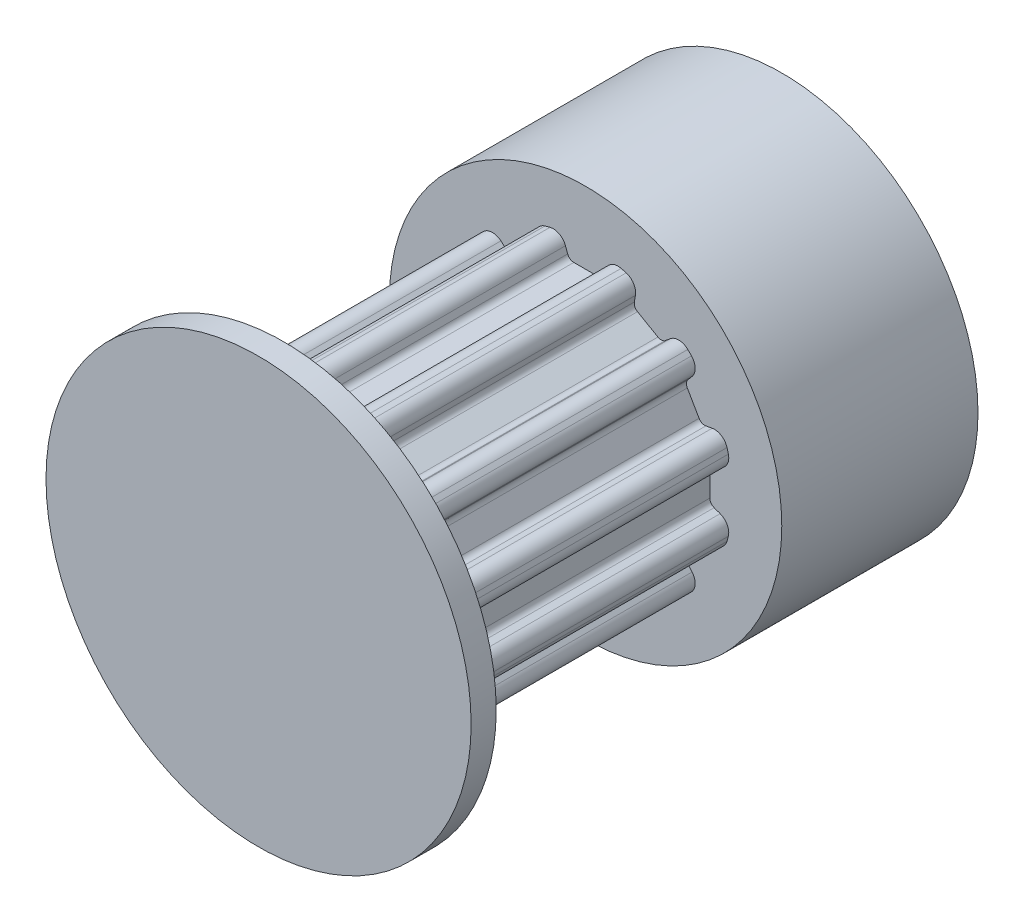
SolidWorks part; units mm, degrees
ref_plane "Front" through (0, 0, 0) normal (0, 0, 1) x (1, 0, 0)
ref_plane "Top" through (0, 0, 0) normal (0, 1, 0) x (1, 0, 0)
ref_plane "Right" through (0, 0, 0) normal (1, 0, 0) x (0, 0, -1)
sketch "support-front-body" plane through (0, 0, 0) normal (0, 0, 1) x (1, 0, 0)
  line L0 (0, 0) -> (0, 4.5) construction
  line L1 (0, 0) -> (0, -4.5) construction
  line L2 (0, 0) -> (4.5, 0) construction
  line L3 (0, 0) -> (-4.5, 0) construction
  circle A0 centre (0, 0) radius 4.5
  dimension "diam-outer" = 9
sketch "support-right-body" plane through (0, 0, 0) normal (1, 0, 0) x (0, 0, -1)
  line L0 (0, 0) -> (10, 0) construction
  line L1 (0, 4.5) -> (10, 4.5)
  line L2 (0, 4.5) -> (0, -4.5)
  line L3 (0, -4.5) -> (10, -4.5)
  line L4 (10, 4.5) -> (10, -4.5)
  dimension "length" = 10
sketch "support-right-chamfer" plane through (0, 0, 0) normal (1, 0, 0) x (0, 0, -1)
  line L0 (0, 0) -> (10, 0) construction
  line L1 (0, -4.5) -> (0, -3.5)
  line L2 (0, 4.5) -> (0, -4.5) construction
  line L4 (0, -3.5) -> (1, -4.5)
  line L5 (0, -4.5) -> (10, -4.5) construction
  line L7 (1, -4.5) -> (0, -4.5)
  line L9 (10, -4.5) -> (9, -4.5)
  line L11 (9, -4.5) -> (10, -3.5)
  line L12 (10, 4.5) -> (10, -4.5) construction
  line L14 (10, -3.5) -> (10, -4.5)
  dimension "height-chamfer-front" = 1
  dimension "angle-chamfer-front" = 45
  dimension "angle-chamfer-back" = 45
  dimension "height-chamfer-back" = 1
sketch "support-right-hub" plane through (0, 0, 0) normal (1, 0, 0) x (0, 0, -1)
  line L0 (16, 0) -> (10, 0) construction
  line L1 (10, 6) -> (16, 6)
  line L2 (10, 6) -> (10, -6)
  line L3 (10, -6) -> (16, -6)
  line L4 (16, 6) -> (16, -6)
  line L6 (0, 0) -> (10, 0) construction
  line L8 (0, 4.5) -> (0, -4.5) construction
  dimension "diam-hub" = 12
  dimension "length-hub" = 6
  dimension "dist-hub" = 10
sketch "support-right-bore" plane through (0, 0, 0) normal (1, 0, 0) x (0, 0, -1)
  line L0 (0, 4.5) -> (0, -4.5) construction
  line L1 (0, 2) -> (16, 2)
  line L2 (0, 2) -> (0, -2)
  line L3 (0, -2) -> (16, -2)
  line L4 (16, 2) -> (16, 0)
  line L5 (16, 0) -> (0, 0) construction
  line L6 (0, 0) -> (10, 0) construction
  line L7 (16, 0) -> (16, -2)
  line L8 (16, -2) -> (16, 2) construction
  dimension "diam-bore" = 4
  dimension "length-bore" = 16
  dimension "angle-bore-bottom" = 180
  dimension "angle-bore" = 90
sketch "support-stop-screw-hole" plane through (0, 0, 0) normal (1, 0, 0) x (0, 0, -1)
  line L1 (6.5667, 11) -> (9.4333, 11)
  line L2 (6.5667, 11) -> (6.5667, -1)
  line L3 (8, -1) -> (9.4333, -1)
  line L4 (9.4333, 11) -> (9.4333, -1)
  line L5 (8, -1) -> (8, 11) construction
  line L6 (8, -1) -> (6.5667, -1)
  line L7 (0, 0) -> (8, 0) construction
  line L8 (0, 4.5) -> (0, -4.5) construction
  dimension "diam-stop-screw-hole" = 2.8665
  dimension "dist-stop-screw-hole" = 8
  dimension "depth-stop-screw-hole" = 12
  dimension "angle-stop-screw-hole" = 180
  dimension "height-stop-screw-hole" = 11
sketch "support-front-keygroove" plane through (0, 0, 0) normal (0, 0, 1) x (1, 0, 0)
  line L0 (0, 0) -> (0, -2) construction
  line L1 (-1, 6) -> (1, 6)
  line L2 (-1, 6) -> (-1, 3.8)
  line L3 (-1, 3.8) -> (1, 3.8)
  line L4 (1, 6) -> (1, 3.8)
  line L5 (0, 0) -> (0, 2) construction
  circle A0 centre (0, 0) radius 2 construction
  dimension "width-keygroove" = 2
  dimension "dist-keygroove" = 8
  dimension "height-keygroove" = 2.2
sketch "support-front-tooth" plane through (0, 0, 0) normal (0, 0, 1) x (1, 0, 0)
  line L0 (0.5479, 3.9316) -> (0.6148, 4.1153)
  line L1 (0, 0) -> (0, 4.5) construction
  line L2 (-0.5479, 3.9316) -> (-0.6148, 4.1153)
  line L3 (-0.36, 3.8) -> (0.36, 3.8)
  line L4 (0, 3.8) -> (-1.0873, 4.3667) construction
  line L5 (0, 3.8) -> (-0.5479, 3.9316) construction
  line L6 (0, 4.5) -> (0.549, 4.3412) construction
  line L7 (0, 4.5) -> (2.4016, 3.8056) construction
  line L8 (0, 4.3667) -> (0, 3.8) construction
  line L9 (1.0873, 4.3667) -> (-1.0873, 4.3667) construction
  line L10 (0, 4.3667) -> (0, 4.9333) construction
  line L11 (0, 0) -> (1.2008, 4.1528) construction
  line L12 (1.411, 4.2731) -> (1.7134, 4.7523)
  line L13 (1.7134, 4.7523) -> (3.5524, 3.5917)
  line L14 (3.5524, 3.5917) -> (3.25, 3.1125)
  line L15 (2.3324, 3.0215) -> (2.7162, 3.1521)
  line L16 (2.3324, 3.0215) -> (1.7236, 3.4057)
  line L17 (1.0873, 4.3667) -> (1.0873, 4.9333)
  line L21 (-1.0873, 4.9333) -> (-1.0873, 4.3667)
  line L22 (1.0873, 4.9333) -> (-1.0873, 4.9333)
  line L23 (1.7236, 3.4057) -> (1.6764, 3.8083)
  line L24 (1.411, 4.2731) -> (1.0873, 4.3667) construction
  line L25 (-0.5479, 3.9316) -> (-0.5, 3.8) construction
  line L26 (-0.5, 3.8) -> (0.5, 3.8) construction
  line L27 (0.5, 3.8) -> (0.5479, 3.9316) construction
  line L28 (0.549, 4.3412) -> (0.9906, 3.9785) construction
  arc A0 (-0.5479, 3.9316) -> (-0.36, 3.8) centre (-0.36, 4) ccw
  circle A1 centre (0, 0) radius 4.5 construction
  arc A2 (0.6148, 4.1153) -> (1.0873, 4.3667) centre (0.9906, 3.9785) cw
  arc A3 (-0.6148, 4.1153) -> (-1.0873, 4.3667) centre (-0.9906, 3.9785) ccw
  arc A4 (0.5479, 3.9316) -> (0.36, 3.8) centre (0.36, 4) cw
  circle A5 centre (0, 0) radius 4.5 construction
  arc A6 (1.6764, 3.8083) -> (1.411, 4.2731) centre (1.2855, 3.8933) ccw
  arc A7 (2.7162, 3.1521) -> (3.25, 3.1125) centre (2.9611, 2.8359) cw
  dimension "D3" = 0.4
  dimension "D2" = 40
  dimension "D1" = 0.2
  dimension "D4" = 1
  dimension "height-tooth" = 0.7
  dimension "pitch" = 2.5
sketch "support-right-flange" plane through (0, 0, 0) normal (1, 0, 0) x (0, 0, -1)
  line L0 (0, 3.25) -> (0, 5.4167)
  line L1 (10, 4.5) -> (10, -4.5) construction
  line L2 (0, 5.4167) -> (1, 5.4167) construction
  line L3 (1, 5.4167) -> (1, 6.5)
  line L4 (0, 6.5) -> (1, 6.5)
  line L5 (1, 5.4167) -> (1, 3.25)
  line L6 (1, 3.25) -> (0, 3.25)
  line L7 (5, 4.5) -> (5, 0) construction
  line L8 (0, 4.5) -> (10, 4.5) construction
  line L9 (0, 5.4167) -> (0, 6.5)
  line L10 (9, 3.25) -> (10, 3.25)
  line L11 (9, 5.4167) -> (9, 3.25)
  line L12 (10, 6.5) -> (9, 6.5)
  line L13 (9, 5.4167) -> (9, 6.5)
  line L14 (10, 5.4167) -> (10, 6.5)
  line L15 (10, 3.25) -> (10, 5.4167)
  line L16 (10, 0) -> (0, 0) construction
  line L17 (10, -3.25) -> (10, -5.4167)
  line L18 (10, -5.4167) -> (10, -6.5)
  line L19 (9, -5.4167) -> (9, -6.5)
  line L20 (10, -6.5) -> (9, -6.5)
  line L21 (9, -5.4167) -> (9, -3.25)
  line L22 (9, -3.25) -> (10, -3.25)
  line L23 (1, -3.25) -> (0, -3.25)
  line L24 (1, -5.4167) -> (1, -3.25)
  line L25 (0, -6.5) -> (1, -6.5)
  line L26 (1, -5.4167) -> (1, -6.5)
  line L27 (0, -5.4167) -> (0, -6.5)
  line L28 (0, -3.25) -> (0, -5.4167)
  line L29 (0, 0) -> (10, 0) construction
  line L30 (0, 5.4167) -> (1, 5.4167) construction
  line L31 (0.5, 3.25) -> (0.5, 4.3333) construction
  line L32 (0.5, 4.3333) -> (0.5, 5.4167) construction
  line L33 (0.5, 6.5) -> (0.5, 5.4167) construction
  line L34 (0, 4.5) -> (10, 4.5) construction
  dimension "angle-flange" = 180
  dimension "thickness-flange" = 1
  dimension "diam-flange-inner" = 6.5
  dimension "diam-flange-outer" = 13
  dimension "width-flange-inner" = 8
sketch "support-right-flange-profile" plane through (0, 0, 0) normal (1, 0, 0) x (0, 0, -1)
  line L0 (0.7668, 6.5) -> (1, 6.5)
  line L2 (1, 6.5) -> (1, 6)
  line L3 (1, 5.4167) -> (1, 3.25) construction
  line L4 (1, 6) -> (0.7668, 6.5)
  line L5 (0, 0) -> (10, 0) construction
  line L6 (5, 0) -> (5, 4.5) construction
  line L7 (9, 6) -> (9.2332, 6.5)
  line L8 (9, 6.5) -> (9, 6)
  line L9 (9.2332, 6.5) -> (9, 6.5)
  dimension "D1" = 25
  dimension "D2" = 0.5
ref_axis "ref-axis-center" through (0, 0, -10) along (0, 0, 1)
ref_plane "ref-plane-front" through (0, 0, 0) normal (0, 0, 1) x (1, 0, 0)
ref_plane "ref-plane-back" through (0, 0, -10) normal (0, 0, 1) x (1, 0, 0)
ref_plane "ref-plane-hub-front" through (0, 0, -10) normal (0, 0, 1) x (1, 0, 0)
ref_plane "ref-plane-hub-back" through (0, 0, -16) normal (0, 0, 1) x (1, 0, 0)
ref_plane "ref-plane-bore-front" through (0, 0, 0) normal (0, 0, 1) x (1, 0, 0)
ref_plane "ref-plane-bore-back" through (0, 0, -16) normal (0, 0, 1) x (1, 0, 0)
ref_plane "ref-plane-stop-screw-hole-top" through (0, 11, 0) normal (0, 1, 0) x (-1, 0, 0)
ref_axis "ref-axis-stop-screw-hole" through (0, 11, -8) along (0, -1, 0)
sketch "Sketch5" plane through (0, 0, 0) normal (1, 0, 0) x (0, 0, -1)
  line L0 (10, 4.5) -> (10, -4.5) construction
  line L1 (0, 4.5) -> (10, 4.5) construction
  line L2 (0, 4.5) -> (0, -4.5) construction
  line L3 (0, 0) -> (10, 0) construction
  line L4 (10, 4.5) -> (10, 0)
  line L5 (0, 4.5) -> (10, 4.5)
  line L6 (0, 4.5) -> (0, 0)
  line L7 (0, 0) -> (10, 0) construction
  line L8 (0, 0) -> (10, 0)
revolve "body" add sketch "Sketch5" angle 360 about L7
sketch "Sketch11" plane through (0, 0, 0) normal (1, 0, 0) x (0, 0, -1)
  line L0 (0, -4.5) -> (0, -3.5) construction
  line L3 (1, -4.5) -> (0, -4.5) construction
  line L5 (0, -3.5) -> (1, -4.5) construction
  line L8 (0, -4.5) -> (0, -3.5)
  line L9 (1, -4.5) -> (0, -4.5)
  line L10 (0, -3.5) -> (1, -4.5)
  line L11 (0, 0) -> (10, 0) construction
  line L12 (0, 0) -> (10, 0) construction
revolve "cut-chamfer-front" [suppressed] cut sketch "Sketch11" angle 360 about L12
sketch "Sketch13" plane through (0, 0, 0) normal (1, 0, 0) x (0, 0, -1)
  line L0 (0, 0) -> (10, 0) construction
  line L1 (10, -4.5) -> (9, -4.5) construction
  line L2 (10, -3.5) -> (10, -4.5) construction
  line L3 (9, -4.5) -> (10, -3.5) construction
  line L4 (0, 0) -> (10, 0) construction
  line L5 (10, -4.5) -> (9, -4.5)
  line L6 (10, -3.5) -> (10, -4.5)
  line L7 (9, -4.5) -> (10, -3.5)
revolve "cut-chamfer-back" [suppressed] cut sketch "Sketch13" angle 360 about L4
sketch "Sketch16" plane through (0, 0, 0) normal (1, 0, 0) x (0, 0, -1)
  line L0 (16, 6) -> (16, -6) construction
  line L1 (10, 6) -> (16, 6) construction
  line L2 (16, 0) -> (10, 0) construction
  line L3 (10, 6) -> (10, -6) construction
  line L4 (16, 6) -> (16, 0)
  line L5 (10, 6) -> (16, 6)
  line L6 (16, 0) -> (10, 0) construction
  line L7 (10, 6) -> (10, 0)
  line L8 (16, 0) -> (10, 0)
revolve "body-hub" add sketch "Sketch16" angle 360 about L6
sketch "Sketch17" plane through (0, 0, 0) normal (1, 0, 0) x (0, 0, -1)
  line L0 (16, 2) -> (16, 0) construction
  line L1 (16, 0) -> (0, 0) construction
  line L2 (0, 2) -> (16, 2) construction
  line L3 (0, 2) -> (0, -2) construction
  line L4 (16, 2) -> (16, 0)
  line L5 (16, 0) -> (0, 0) construction
  line L6 (0, 2) -> (16, 2)
  line L7 (0, 2) -> (0, 0)
  line L8 (16, 0) -> (0, 0)
revolve "body-bore" [suppressed] cut sketch "Sketch17" angle 360 about L5
sketch "Sketch19" plane through (0, 0, 0) normal (1, 0, 0) x (0, 0, -1)
  line L0 (6.5667, 11) -> (9.4333, 11) construction
  line L1 (8, -1) -> (8, 11) construction
  line L2 (9.4333, 11) -> (9.4333, -1) construction
  line L3 (8, -1) -> (9.4333, -1) construction
  line L4 (8, 11) -> (9.4333, 11)
  line L5 (8, -1) -> (8, 11) construction
  line L6 (9.4333, 11) -> (9.4333, -1)
  line L7 (8, -1) -> (9.4333, -1)
  line L8 (8, -1) -> (8, 11)
revolve "body-stop-screw-hole" [suppressed] cut sketch "Sketch19" angle 360 about L5
pattern_circular "pattern-stop-screw-hole" [suppressed] count 2 every 90 about axis through (0, 0, -10) along (0, 0, 1)
sketch "Sketch21" plane through (0, 0, 0) normal (0, 0, 1) x (1, 0, 0)
  line L0 (-1, 6) -> (1, 6) construction
  line L1 (-1, 6) -> (-1, 3.8) construction
  line L2 (-1, 3.8) -> (1, 3.8) construction
  line L3 (1, 6) -> (1, 3.8) construction
  line L4 (-1, 6) -> (1, 6)
  line L5 (-1, 6) -> (-1, 3.8)
  line L6 (-1, 3.8) -> (1, 3.8)
  line L7 (1, 6) -> (1, 3.8)
extrude "cut-keygroove" [suppressed] cut sketch "Sketch21" against normal up to surface (17.5 mm away)
sketch "Sketch23" plane through (0, 0, 0) normal (0, 0, 1) x (1, 0, 0)
  line L0 (0.5479, 3.9316) -> (0.6148, 4.1153) construction
  line L1 (-0.5479, 3.9316) -> (-0.6148, 4.1153) construction
  line L2 (-1.0873, 4.9333) -> (-1.0873, 4.3667) construction
  line L3 (1.0873, 4.9333) -> (-1.0873, 4.9333) construction
  line L4 (1.0873, 4.3667) -> (1.0873, 4.9333) construction
  line L6 (0.5479, 3.9316) -> (0.6148, 4.1153)
  line L7 (-0.5479, 3.9316) -> (-0.6148, 4.1153)
  line L8 (-1.0873, 4.9333) -> (-1.0873, 4.3667)
  line L9 (1.0873, 4.9333) -> (-1.0873, 4.9333)
  line L10 (1.0873, 4.3667) -> (1.0873, 4.9333)
  line L11 (-0.36, 3.8) -> (0.36, 3.8) construction
  line L12 (-0.36, 3.8) -> (0.36, 3.8)
  arc A0 (0.36, 3.8) -> (0.5479, 3.9316) centre (0.36, 4) ccw construction
  arc A1 (-0.5479, 3.9316) -> (-0.36, 3.8) centre (-0.36, 4) ccw construction
  arc A2 (-0.6148, 4.1153) -> (-1.0873, 4.3667) centre (-0.9906, 3.9785) ccw construction
  arc A3 (1.0873, 4.3667) -> (0.6148, 4.1153) centre (0.9906, 3.9785) ccw construction
  arc A4 (0.36, 3.8) -> (0.5479, 3.9316) centre (0.36, 4) ccw
  arc A5 (-0.5479, 3.9316) -> (-0.36, 3.8) centre (-0.36, 4) ccw
  arc A6 (-0.6148, 4.1153) -> (-1.0873, 4.3667) centre (-0.9906, 3.9785) ccw
  arc A7 (1.0873, 4.3667) -> (0.6148, 4.1153) centre (0.9906, 3.9785) ccw
extrude "cut-tooth" cut sketch "Sketch23" against normal up to surface (10 mm away) up to plane "ref-plane-back"
pattern_circular "pattern-tooth" count 12 over 360 about axis through (0, 0, -10) along (0, 0, 1) of "cut-tooth"
sketch "Sketch25" plane through (0, 0, 0) normal (1, 0, 0) x (0, 0, -1)
  line L0 (0, 0) -> (10, 0) construction
  line L1 (1, 3.25) -> (0, 3.25) construction
  line L2 (1, 5.4167) -> (1, 3.25) construction
  line L4 (0, 6.5) -> (1, 6.5) construction
  line L5 (0, 5.4167) -> (0, 6.5) construction
  line L6 (0, 3.25) -> (0, 5.4167) construction
  line L7 (0, 0) -> (10, 0) construction
  line L8 (1, 3.25) -> (0, 3.25)
  line L9 (1, 5.4167) -> (1, 3.25)
  line L10 (0, 6.5) -> (1, 6.5)
  line L11 (1, 5.4167) -> (1, 6.5) construction
  line L12 (0, 5.4167) -> (0, 6.5)
  line L13 (0, 3.25) -> (0, 5.4167)
  line L14 (1, 5.4167) -> (1, 6.5)
revolve "body-flange-front" add sketch "Sketch25" angle 360 about L7
sketch "Sketch26" plane through (0, 0, 0) normal (1, 0, 0) x (0, 0, -1)
  line L0 (10, 0) -> (0, 0) construction
  line L1 (9, 3.25) -> (10, 3.25) construction
  line L2 (9, 5.4167) -> (9, 3.25) construction
  line L4 (10, 6.5) -> (9, 6.5) construction
  line L5 (10, 5.4167) -> (10, 6.5) construction
  line L6 (10, 3.25) -> (10, 5.4167) construction
  line L7 (10, 0) -> (0, 0) construction
  line L8 (9, 3.25) -> (10, 3.25)
  line L9 (9, 5.4167) -> (9, 3.25)
  line L10 (10, 6.5) -> (9, 6.5)
  line L11 (9, 5.4167) -> (9, 6.5) construction
  line L12 (10, 5.4167) -> (10, 6.5)
  line L13 (10, 3.25) -> (10, 5.4167)
  line L14 (9, 5.4167) -> (9, 6.5)
revolve "body-flange-back" [suppressed] add sketch "Sketch26" angle 360 about L7
sketch "Sketch28" plane through (0, 0, 0) normal (1, 0, 0) x (0, 0, -1)
  line L0 (1, 6.5) -> (1, 6) construction
  line L1 (0.7668, 6.5) -> (1, 6.5) construction
  line L2 (1, 6) -> (0.7668, 6.5) construction
  line L3 (1, 6.5) -> (1, 6)
  line L4 (0.7668, 6.5) -> (1, 6.5)
  line L5 (1, 6) -> (0.7668, 6.5)
  line L6 (10, 0) -> (0, 0) construction
  line L7 (10, 0) -> (0, 0) construction
revolve "body-flange-profile-front" cut sketch "Sketch28" angle 360 about L7
sketch "Sketch29" plane through (0, 0, 0) normal (1, 0, 0) x (0, 0, -1)
  line L0 (10, 0) -> (0, 0) construction
  line L1 (9, 6.5) -> (9, 6) construction
  line L2 (9.2332, 6.5) -> (9, 6.5) construction
  line L3 (9, 6) -> (9.2332, 6.5) construction
  line L4 (10, 0) -> (0, 0) construction
  line L5 (9, 6.5) -> (9, 6)
  line L6 (9.2332, 6.5) -> (9, 6.5)
  line L7 (9, 6) -> (9.2332, 6.5)
revolve "body-flange-profile-back" [suppressed] cut sketch "Sketch29" angle 360 about L4
sketch "support-right-cut-body" plane through (0, 0, 0) normal (1, 0, 0) x (0, 0, -1)
  line L0 (10, 4.5) -> (10, -4.5) construction
  line L1 (0, 4.5) -> (10, 4.5) construction
  line L2 (0, 4.5) -> (0, -4.5) construction
  line L3 (0, -4.5) -> (10, -4.5) construction
  line L4 (10, 4.5) -> (10, -4.5) construction
  line L5 (0, 4.5) -> (0, -4.5) construction
  line L6 (0, 4.5) -> (10, 4.5) construction
  line L7 (0, -4.5) -> (10, -4.5) construction
  line L8 (10, 0) -> (0, 0) construction
  line L9 (5, 4.5) -> (5, -4.5) construction
  line L10 (10, 58.5) -> (6.6667, 58.5)
  line L11 (10, 58.5) -> (10, -58.5)
  line L12 (10, -58.5) -> (6.6667, -58.5)
  line L13 (6.6667, 58.5) -> (6.6667, -58.5)
  line L14 (0, 58.5) -> (3.3333, 58.5)
  line L15 (0, 58.5) -> (0, -58.5)
  line L16 (0, -58.5) -> (3.3333, -58.5)
  line L17 (3.3333, 58.5) -> (3.3333, -58.5)
  line L18 (6.6667, 58.5) -> (3.3333, 58.5) construction
  line L19 (3.3333, -58.5) -> (5, -58.5) construction
  line L21 (10, 6) -> (6.6667, 6)
  line L23 (10, 6) -> (16, 6) construction
  line L24 (10, -6) -> (6.6667, -6)
  line L25 (0, 6) -> (3.3333, 6)
  line L26 (0, -6) -> (3.3333, -6)
  dimension "diam" = 117
sketch "support-front-cut-body" plane through (0, 0, 0) normal (0, 0, 1) x (1, 0, 0)
  line L0 (58.5, 0) -> (-58.5, 0) construction
  line L1 (0, 58.5) -> (0, 6) construction
  line L2 (0, 4.5) -> (0, -4.5) construction
  line L4 (0, 58.5) -> (-54.972, -20.0082) construction
  line L6 (0, -6) -> (0, -58.5) construction
  circle A0 centre (0, 32.25) radius 15.0564
  circle A1 centre (0, 0) radius 58.5 construction
  circle A2 centre (0, 0) radius 6 construction
  dimension "D1" = 35
sketch "Sketch31" plane through (0, 0, 0) normal (1, 0, 0) x (0, 0, -1)
  line L0 (0, 58.5) -> (0, -58.5) construction
  line L1 (0, 58.5) -> (3.3333, 58.5) construction
  line L2 (3.3333, 58.5) -> (3.3333, -58.5) construction
  line L3 (10, 58.5) -> (10, -58.5) construction
  line L4 (10, 58.5) -> (6.6667, 58.5) construction
  line L5 (6.6667, 58.5) -> (6.6667, -58.5) construction
  line L7 (0, 58.5) -> (0, 6)
  line L8 (0, 58.5) -> (3.3333, 58.5)
  line L9 (3.3333, 58.5) -> (3.3333, 6)
  line L10 (10, 58.5) -> (10, 6)
  line L11 (10, 58.5) -> (6.6667, 58.5)
  line L12 (6.6667, 58.5) -> (6.6667, 6)
  line L13 (10, 6) -> (6.6667, 6)
  line L14 (10, 6) -> (6.6667, 6) construction
  line L15 (3.3333, 6) -> (0, 6)
  line L16 (0, 0) -> (10, 0) construction
  line L17 (10, 0) -> (0, 0) construction
revolve "cut-body" [suppressed] cut sketch "Sketch31" angle 360 about L16
sketch "Sketch33" plane through (0, 0, 0) normal (0, 0, 1) x (1, 0, 0)
  circle A0 centre (0, 32.25) radius 15.0564 construction
  circle A1 centre (0, 32.25) radius 15.0564
extrude "cut-front-body" [suppressed] cut sketch "Sketch33" against normal through all
pattern_circular "pattern-cut-front-body" [suppressed] count 6 over 360 about axis through (0, 0, -10) along (0, 0, 1)
